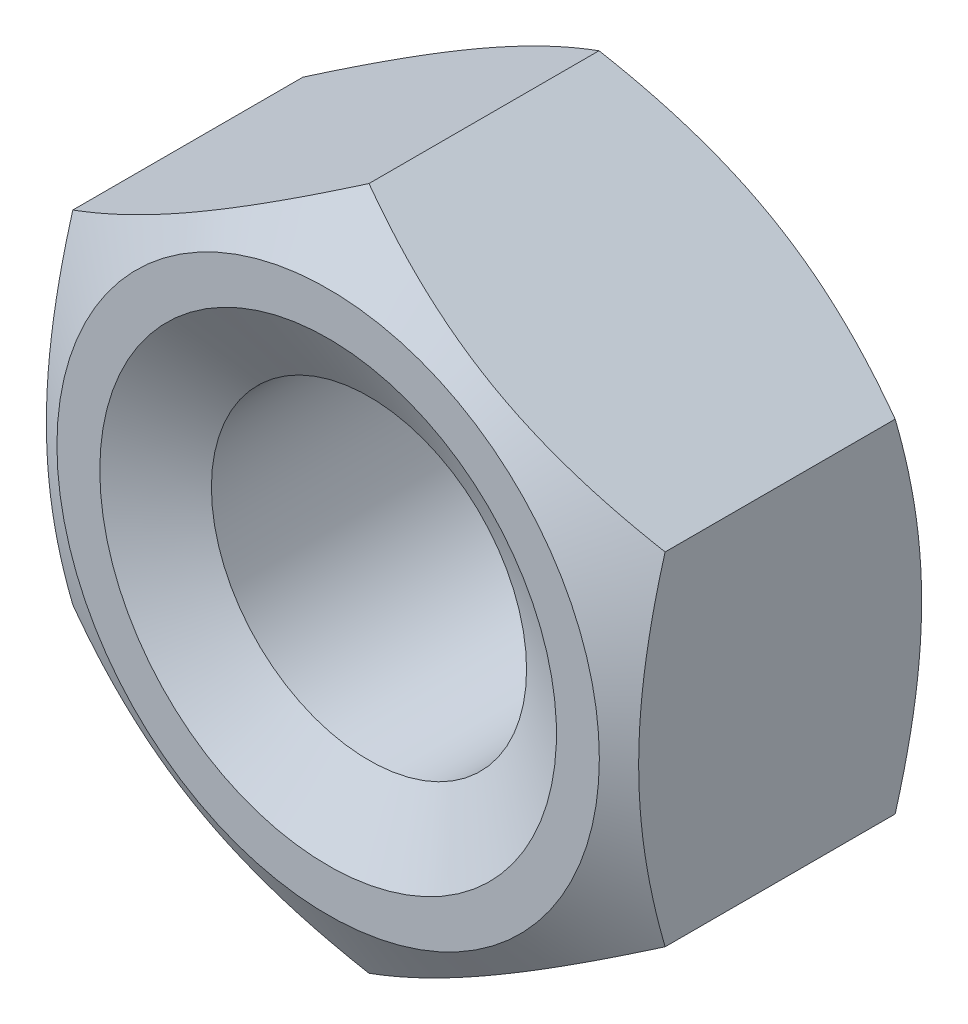
SolidWorks part; units mm, degrees
other "Ссылка на сопряжения"
material "AISI 316 Нержавеющая сталь, лист (SS)"
ref_plane "Плоскость1" through (0, 0, 0) normal (0, 0, 1) x (1, 0, 0)
ref_plane "Плоскость2" through (0, 0, 0) normal (0, 1, 0) x (1, 0, 0)
ref_plane "Плоскость3" through (0, 0, 0) normal (1, 0, 0) x (0, 0, -1)
sketch "Эскиз1" plane through (0, 0, 0) normal (0, 0, 1) x (1, 0, 0)
  line L1 (0, 10.9697) -> (-9.5, 5.4848)
  line L2 (-9.5, 5.4848) -> (-9.5, -5.4848)
  line L3 (-9.5, -5.4848) -> (0, -10.9697)
  line L4 (0, -10.9697) -> (9.5, -5.4848)
  line L5 (9.5, -5.4848) -> (9.5, 5.4848)
  line L6 (9.5, 5.4848) -> (0, 10.9697)
  circle A0 centre (0, 0) radius 9.5 construction
  circle A1 centre (0, 0) radius 5.055
  dimension "rezba" = 10.11
  dimension "S" = 19
extrude "Основание-Вытянуть" add sketch "Эскиз1" along normal blind 10
cosmetic thread "Условное изображение резьбы1" parameters "d"=12
sketch "Эскиз2" plane through (0, 0, 0) normal (1, 0, 0) x (0, 0, -1)
  line L0 (-10, 5.4848) -> (-10, 10.9697) construction
  line L1 (-10, 10.9697) -> (0, 10.9697) construction
  line L2 (-10, 8.7) -> (-10, 10.9697)
  line L3 (-10, 10.9697) -> (-8.6896, 10.9697)
  line L4 (-10, 8.7) -> (-8.6896, 10.9697)
  line L5 (0, 0) -> (-10, 0) construction
  line L6 (-10, 0) -> (0, 0) construction
  line L7 (-10, -5.4848) -> (-10, 5.4848) construction
  line L8 (0, 5.055) -> (-10, 5.055) construction
  line L9 (-8.6896, 5.055) -> (-10, 5.055)
  line L10 (-10, 7.3247) -> (-8.6896, 5.055)
  line L11 (-10, 7.3247) -> (-10, 5.055)
  line L12 (-5, 0) -> (-5, 3.9594) construction
  line L13 (0, 7.3247) -> (0, 5.055)
  line L14 (0, 7.3247) -> (-1.3104, 5.055)
  line L15 (-1.3104, 5.055) -> (0, 5.055)
  line L16 (0, 8.7) -> (-1.3104, 10.9697)
  line L17 (0, 10.9697) -> (-1.3104, 10.9697)
  line L18 (0, 8.7) -> (0, 10.9697)
  dimension "D1" = 17.4
  dimension "_" = 30
revolve "Вырез-Повернуть1" cut sketch "Эскиз2" angle 360 about L5
revolve "Скрытый" add sketch "Эскиз2<3>" angle 360 about L5 region at (0, 5.8116, 0.4368)
sketch "Эскиз2<3>" plane through (0, 0, 0) normal (1, 0, 0) x (0, 0, -1) same geometry as "Эскиз2"
